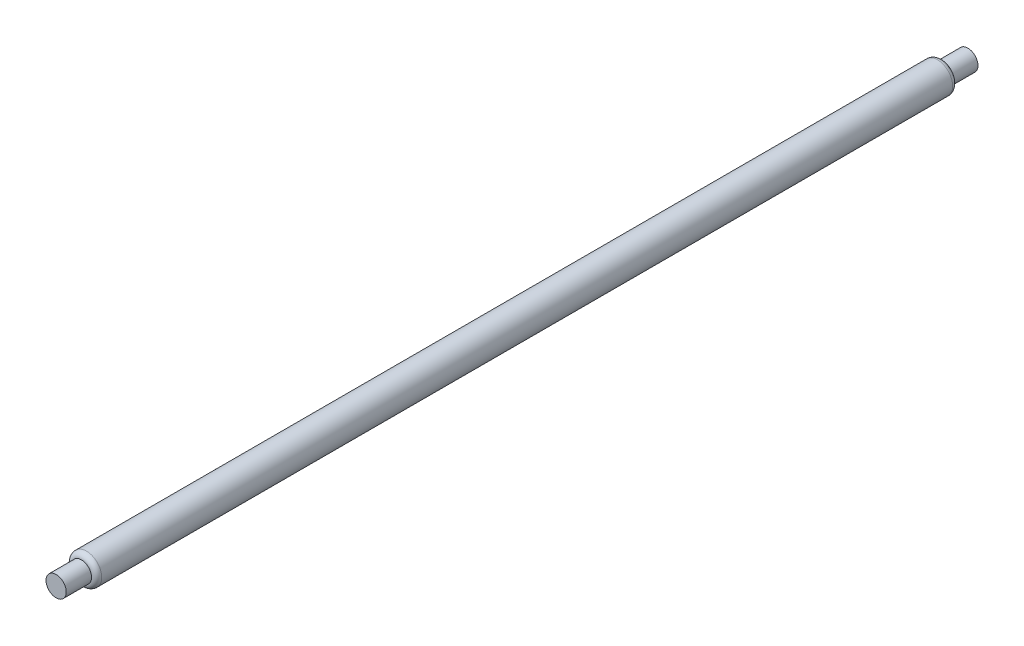
SolidWorks part; units mm, degrees
ref_plane "Front" through (0, 0, 0) normal (0, 0, 1) x (1, 0, 0)
ref_plane "Top" through (0, 0, 0) normal (0, 1, 0) x (1, 0, 0)
ref_plane "Right" through (0, 0, 0) normal (1, 0, 0) x (0, 0, -1)
sketch "Sketch1" plane through (0, 0, 0) normal (0, 0, 1) x (1, 0, 0)
  circle A0 centre (0, 0) radius 6
  dimension "D1" = 12
extrude "Boss-Extrude1" add sketch "Sketch1" along normal mid plane 360
sketch "Sketch2" plane through (0, 0, 180) normal (0, 0, 1) x (1, 0, 0)
  circle A0 centre (0, 0) radius 4
  circle A1 centre (0, 0) radius 6
  circle A2 centre (0, 0) radius 6 construction
  dimension "D1" = 8
extrude "Cut-Extrude1" cut sketch "Sketch2" against normal blind 10
fillet "Fillet1" radius 2 1 edges at (6, 0, 170)
mirror "Mirror1" about plane through (0, 0, 0) normal (0, 0, 1) of "Cut-Extrude1", "Fillet1"
equation "\"d\"= 12"
equation "\"l\"= 360"
equation "\"D1@Sketch1\"= \"d\""
equation "\"D1@Boss-Extrude1\"=\"l\""
equation "\"d_end\"= 8"
equation "\"D1@Sketch2\"=\"d_end\""
equation "\"l_end\"= 10"
equation "\"D1@Cut-Extrude1\"=\"l_end\""
equation "\"D1@Fillet1\"=(\"d\" - \"d_end\") / 2"
